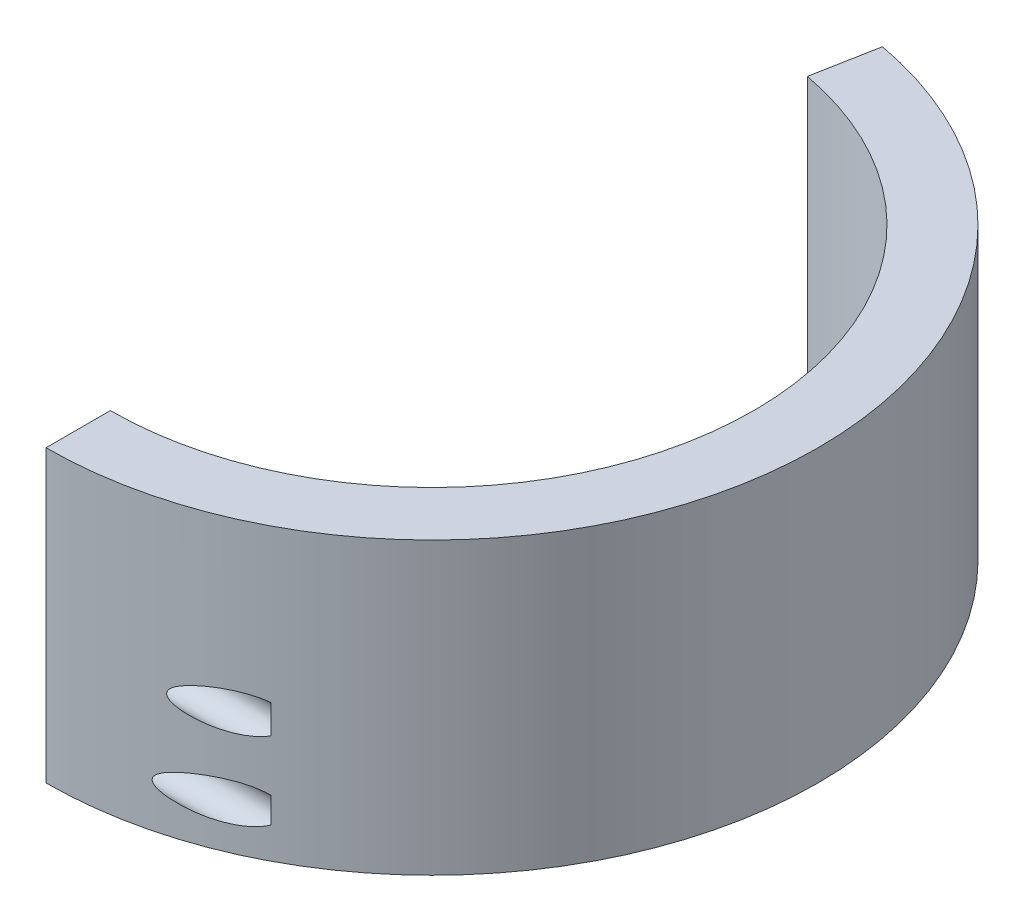
SolidWorks part; units mm, degrees
ref_plane "Front Plane" through (0, 0, 0) normal (0, 0, 1) x (1, 0, 0)
ref_plane "Top Plane" through (0, 0, 0) normal (0, 1, 0) x (1, 0, 0)
ref_plane "Right Plane" through (0, 0, 0) normal (1, 0, 0) x (0, 0, -1)
sketch "Sketch1" plane through (0, 0, 0) normal (0, 1, 0) x (1, 0, 0)
  line L0 (70.4982, 37.4518) -> (69.3319, 31.2098)
  line L1 (63.5, -31.75) -> (63.5, -38.1)
  arc A0 (63.5, -38.1) -> (70.4982, 37.4518) centre (63.5, 0) ccw
  arc A1 (69.8182, -31.115) -> (75.4259, 29.4251) centre (63.5, 0) ccw
  arc A2 (69.3319, 31.2098) -> (75.4259, 29.4251) centre (63.5, 0) cw
  arc A3 (69.8182, -31.115) -> (63.5, -31.75) centre (63.5, 0) cw
  point P8 (69.3319, 0)
extrude "Boss-Extrude1" add sketch "Sketch1" along normal blind 27.94
sketch "Sketch2" plane through (63.5, 0, 0) normal (-1, 0, 0) x (0, 0, 1)
  circle A0 centre (34.8215, 11.4187) radius 1.5
  circle A1 centre (35.0699, 3.6543) radius 1.5549
  circle A2 centre (-34.5328, 13.1948) radius 1.5192
  circle A3 centre (-34.5328, 3.6543) radius 1.5
  circle A4 centre (34.8215, 11.4187) radius 1.8175
  circle A5 centre (35.0699, 3.6543) radius 1.8724
  circle A6 centre (-34.5328, 13.1948) radius 1.8367
  circle A7 centre (-34.5328, 3.6543) radius 1.8175
extrude "Cut-Extrude1" cut sketch "Sketch2" against normal blind 17.78 and the other way blind 17.78 contours A0 | A1 | A2 | A3 region at (63.5, 11.4187, 34.8215) region at (63.5, 3.6543, 35.0699) region at (63.5, 13.1948, -34.5328) region at (63.5, 3.6543, -34.5328)
extrude "Cut-Extrude2" cut sketch "Sketch2<3>" against normal blind 17.78 contours A4 A0 | A5 A1 | A6 A2 | A7 A3 region at (63.5, 11.4187, 33.0554) region at (63.5, 3.6543, 33.2505) region at (63.5, 13.1948, -36.3175) region at (63.5, 3.6543, -36.2989)
sketch "Sketch2<3>" plane through (63.5, 0, 0) normal (-1, 0, 0) x (0, 0, 1) same geometry as "Sketch2"
extrude "Boss-Extrude2" add sketch "Sketch1<2>" against normal blind 0.7112
sketch "Sketch1<2>" plane through (0, 0, 0) normal (0, 1, 0) x (1, 0, 0) same geometry as "Sketch1"
